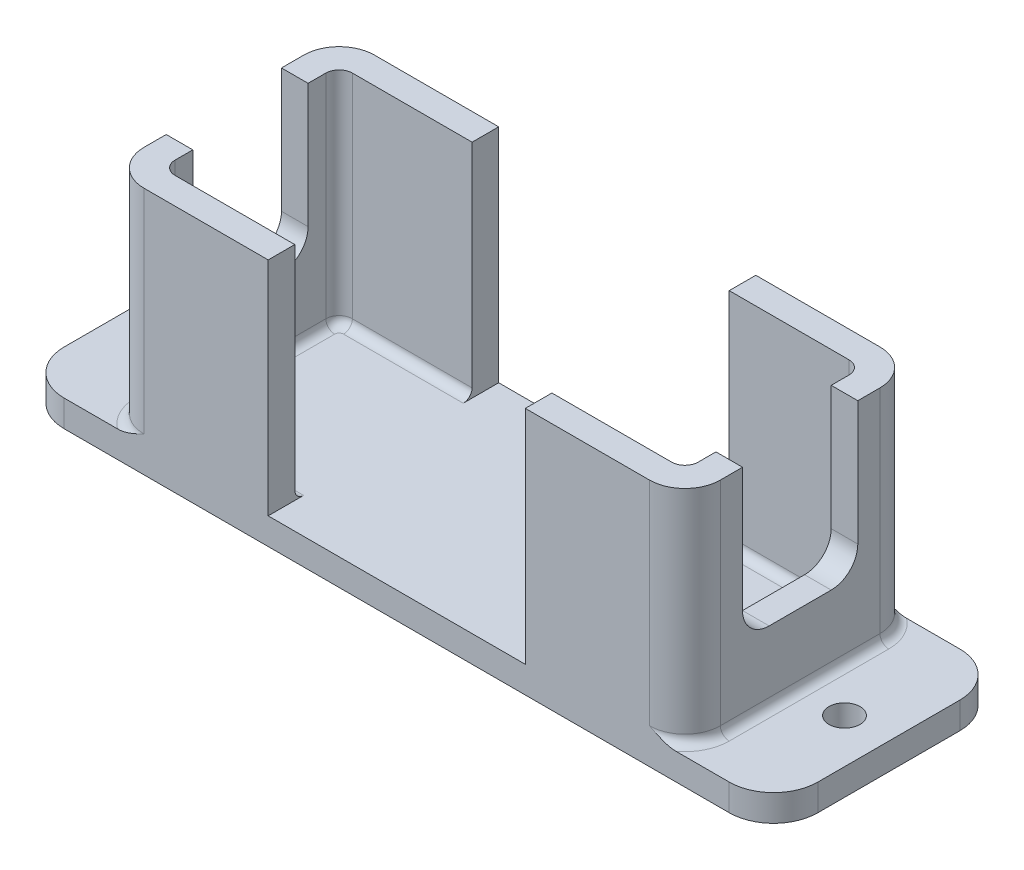
SolidWorks part; units mm, degrees
ref_plane "Alzado" through (0, 0, 0) normal (0, 0, 1) x (1, 0, 0)
ref_plane "Planta" through (0, 0, 0) normal (0, 1, 0) x (1, 0, 0)
ref_plane "Vista lateral" through (0, 0, 0) normal (1, 0, 0) x (0, 0, -1)
sketch "Croquis1" plane through (0, 0, 0) normal (0, 1, 0) x (1, 0, 0)
  line L0 (0, -13) -> (0, 13)
  line L1 (0, 13) -> (18, 13)
  line L2 (18, 13) -> (18, 10)
  line L3 (18, 10) -> (3, 10)
  line L4 (3, 10) -> (3, -10)
  line L5 (3, -10) -> (18, -10)
  line L6 (18, -10) -> (18, -13)
  line L7 (18, -13) -> (0, -13)
  line L8 (32.5, 13) -> (32.5, -12.2003) construction
  line L9 (47, -10) -> (47, -13)
  line L10 (62, -10) -> (47, -10)
  line L11 (62, 10) -> (62, -10)
  line L12 (47, 10) -> (62, 10)
  line L13 (47, 13) -> (47, 10)
  line L14 (65, 13) -> (47, 13)
  line L15 (65, -13) -> (65, 13)
  line L16 (47, -13) -> (65, -13)
  point P3 (0, 0)
  dimension "D1" = 3
  dimension "D2" = 3
  dimension "D3" = 3
  dimension "D4" = 20
  dimension "D5" = 15
  dimension "D6" = 14.5
extrude "Saliente-Extruir1" add sketch "Croquis1" along normal blind 25
sketch "Croquis2" plane through (0, 0, 0) normal (0, -1, 0) x (1, 0, 0)
  line L12 (-10, -13) -> (75, -13)
  line L13 (-10, -13) -> (-10, 13)
  line L14 (-10, 13) -> (75, 13)
  line L15 (75, -13) -> (75, 13)
  line L16 (47, 13) -> (65, 13) construction
  line L17 (18, -13) -> (0, -13) construction
  line L18 (0, -13) -> (0, 13) construction
  line L19 (65, 13) -> (65, -13) construction
  dimension "D1" = 10
  dimension "D2" = 10
extrude "Saliente-Extruir2" add sketch "Croquis2" along normal blind 3
sketch "Croquis3" plane through (0, 0, 0) normal (-1, 0, 0) x (0, 0, 1)
  line L0 (-13, 25) -> (13, 25) construction
  line L1 (-6.5, 25) -> (6.5, 25)
  line L2 (-6.5, 25) -> (-6.5, 8)
  line L3 (-6.5, 8) -> (6.5, 8)
  line L4 (6.5, 25) -> (6.5, 8)
  line L6 (-13, 0) -> (13, 0) construction
  point P6 (0, 25)
  dimension "D1" = 13
  dimension "D2" = 8
ref_plane "Plano2" through (32.5, 0, 0) normal (1, 0, 0) x (0, 0, -1)
extrude "Cortar-Extruir2" cut sketch "Croquis3" against normal through all
fillet "Redondeo1" radius 5 4 edges at (-10, -1.5, 13) (-10, -1.5, -13) (75, -1.5, -13) (75, -1.5, 13)
fillet "Redondeo2" radius 3 2 edges at (1.5, 8, -6.5) (1.5, 8, 6.5)
fillet "Redondeo3" radius 3 2 edges at (63.5, 8, 6.5) (63.5, 8, -6.5)
fillet "Redondeo4" radius 1.5 2 edges at (3, 12.5, -10) (3, 12.5, 10)
fillet "Redondeo5" radius 4 2 edges at (0, 12.5, 13) (0, 12.5, -13)
fillet "Redondeo6" radius 4 2 edges at (65, 12.5, -13) (65, 12.5, 13)
fillet "Redondeo7" radius 1.5 2 edges at (62, 12.5, 10) (62, 12.5, -10)
sketch "Croquis5" plane through (0, 0, 0) normal (0, 1, 0) x (1, 0, 0)
  line L2 (75, 8) -> (75, -8) construction
  line L3 (-10, -8) -> (-10, 8) construction
  circle A0 centre (70, 0) radius 1.75
  circle A1 centre (-5, 0) radius 1.75
  point P9 (0, 0)
  dimension "D1" = 3.5
  dimension "D2" = 5
  dimension "D3" = 5
extrude "Cortar-Extruir3" cut sketch "Croquis5" against normal through all
combine bodies "Combinar1" operation type add bodies to combine 112 111
fillet "Redondeo8" radius 1 6 edges at (1.1716, 0, -11.8284) (1.1716, 0, 11.8284) (0, 0, 0) (63.8284, 0, 11.8284) (63.8284, 0, -11.8284) (65, 0, 0)
fillet "Redondeo10" radius 1 10 edges at (53.75, 0, -10) (61.5607, 0, -9.5607) (53.75, 0, 10) (61.5607, 0, 9.5607) (11.25, 0, 10) (3.4393, 0, 9.5607) (11.25, 0, -10) (3.4393, 0, -9.5607) (62, 0, 0) (3, 0, 0)
